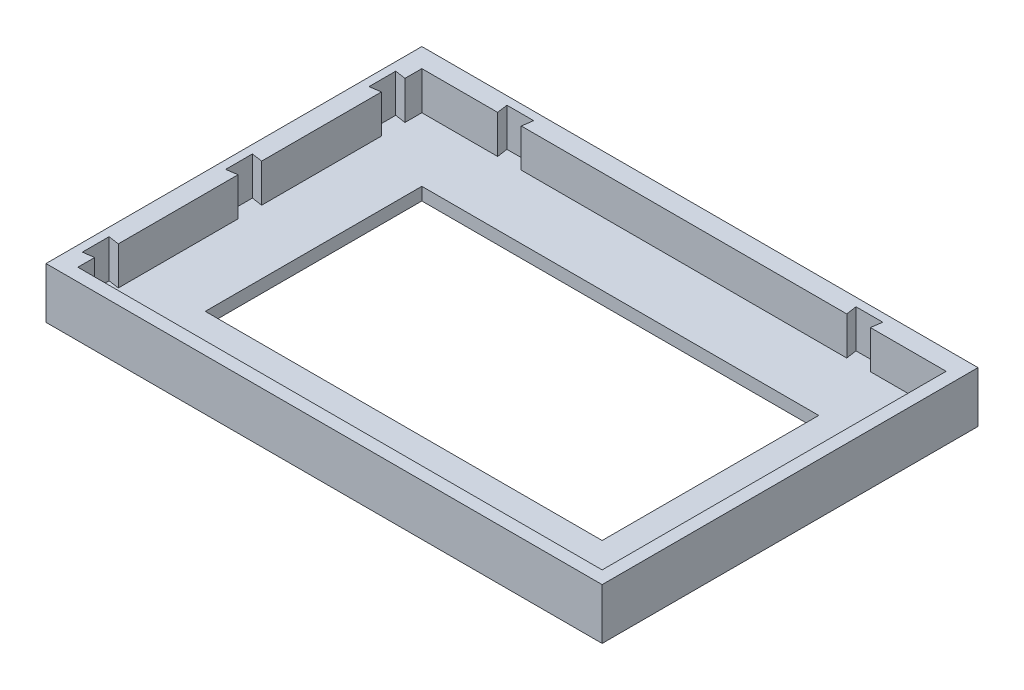
SolidWorks part; units mm, degrees
ref_plane "Front Plane" through (0, 0, 0) normal (0, 0, 1) x (1, 0, 0)
ref_plane "Top Plane" through (0, 0, 0) normal (0, 1, 0) x (1, 0, 0)
ref_plane "Right Plane" through (0, 0, 0) normal (1, 0, 0) x (0, 0, -1)
sketch "Sketch1" plane through (0, 0, 0) normal (0, 1, 0) x (1, 0, 0)
  line L1 (-38.2233, -33.5464) -> (49.0767, -33.5464)
  line L2 (-38.2233, -33.5464) -> (-38.2233, 25.4536)
  line L3 (-38.2233, 25.4536) -> (49.0767, 25.4536)
  line L4 (49.0767, -33.5464) -> (49.0767, 25.4536)
  dimension "D1" = 87.3
  dimension "D2" = 59
extrude "Boss-Extrude1" add sketch "Sketch1" along normal blind 8
sketch "Sketch2" plane through (0, 8, 0) normal (0, 1, 0) x (1, 0, 0)
  line L0 (49.0767, 25.4536) -> (-38.2233, 25.4536) construction
  line L1 (-35.2233, -31.5464) -> (47.0767, -31.5464)
  line L2 (-35.2233, -31.5464) -> (-35.2233, 22.4536)
  line L3 (-35.2233, 22.4536) -> (47.0767, 22.4536)
  line L4 (47.0767, -31.5464) -> (47.0767, 22.4536)
  line L5 (-38.2233, -33.5464) -> (49.0767, -33.5464) construction
  line L6 (-38.2233, 25.4536) -> (-38.2233, -33.5464) construction
  line L7 (49.0767, -33.5464) -> (49.0767, 25.4536) construction
  dimension "D1" = 3
  dimension "D2" = 2
  dimension "D3" = 3
  dimension "D4" = 2
extrude "Cut-Extrude1" cut sketch "Sketch2" against normal offset from surface (6 mm away) 2 up to face at (5.4267, 0, 4.0464)
sketch "Sketch3" plane through (0, 8, 0) normal (0, 1, 0) x (1, 0, 0)
  line L0 (-35.2233, -28.8964) -> (-36.9233, -29.1464)
  line L1 (-35.2233, 22.4536) -> (-35.2233, -31.5464) construction
  line L2 (-36.9233, -29.1464) -> (-36.9233, -24.9464)
  line L3 (-36.9233, -24.9464) -> (-35.2233, -25.1964)
  line L4 (-35.2233, 22.4536) -> (-35.2233, -31.5464) construction
  line L5 (-35.2233, -25.1964) -> (-35.2233, -28.8964)
  line L6 (-35.2233, -31.5464) -> (47.0767, -31.5464) construction
  line L7 (-35.2233, -6.3964) -> (-36.9233, -6.6464)
  line L8 (-36.9233, -6.6464) -> (-36.9233, -2.4464)
  line L9 (-36.9233, -2.4464) -> (-35.2233, -2.6964)
  line L10 (-35.2233, -2.6964) -> (-35.2233, -6.3964)
  line L11 (-35.2233, 16.1036) -> (-36.9233, 15.8536)
  line L12 (-36.9233, 15.8536) -> (-36.9233, 20.0536)
  line L13 (-36.9233, 20.0536) -> (-35.2233, 19.8036)
  line L14 (-35.2233, 19.8036) -> (-35.2233, 16.1036)
  line L15 (-35.2233, -28.8964) -> (-35.2233, -6.3964) construction
  line L16 (35.1767, 22.4536) -> (31.4767, 22.4536)
  line L17 (47.0767, 22.4536) -> (-35.2233, 22.4536) construction
  line L18 (-23.3233, 22.4536) -> (-23.5733, 24.1536)
  line L19 (-23.5733, 24.1536) -> (-19.3733, 24.1536)
  line L20 (-19.3733, 24.1536) -> (-19.6233, 22.4536)
  line L21 (47.0767, 22.4536) -> (-35.2233, 22.4536) construction
  line L22 (-19.6233, 22.4536) -> (-23.3233, 22.4536)
  line L23 (31.4767, 22.4536) -> (31.2267, 24.1536)
  line L24 (31.2267, 24.1536) -> (35.4267, 24.1536)
  line L25 (35.4267, 24.1536) -> (35.1767, 22.4536)
  line L26 (-19.6233, 22.4536) -> (35.1767, 22.4536) construction
  point P9 (-36.9233, -27.0464)
  point P10 (-35.2233, -27.0464)
  point P28 (-21.4733, 22.4536)
  point P32 (-21.4733, 24.1536)
  dimension "D1" = 4.2
  dimension "D2" = 1.7
  dimension "D3" = 3.7
  dimension "D4" = 4.5
  dimension "D6" = 22.5
  dimension "D7" = 4.2
  dimension "D8" = 1.7
  dimension "D9" = 13.75
  dimension "D10" = 3.7
  dimension "D12" = 54.8
  dimension "D5" = 3
  dimension "D11" = 2
extrude "Cut-Extrude2" cut sketch "Sketch3" against normal up to surface (6 mm away) up to face at (5.9267, 2, 4.5464)
sketch "Sketch4" plane through (0, 2, 0) normal (0, 1, 0) x (1, 0, 0)
  line L0 (-35.2233, 16.1036) -> (-35.2233, -2.6964) construction
  line L1 (-25.2233, -21.5464) -> (37.0767, -21.5464)
  line L2 (-25.2233, -21.5464) -> (-25.2233, 12.4536)
  line L3 (-25.2233, 12.4536) -> (37.0767, 12.4536)
  line L4 (37.0767, -21.5464) -> (37.0767, 12.4536)
  line L5 (31.4767, 22.4536) -> (-19.6233, 22.4536) construction
  line L6 (47.0767, -31.5464) -> (47.0767, 22.4536) construction
  line L7 (-35.2233, -31.5464) -> (47.0767, -31.5464) construction
  dimension "D1" = 10
  dimension "D2" = 10
  dimension "D3" = 10
  dimension "D4" = 10
extrude "Cut-Extrude3" cut sketch "Sketch4" against normal through all
